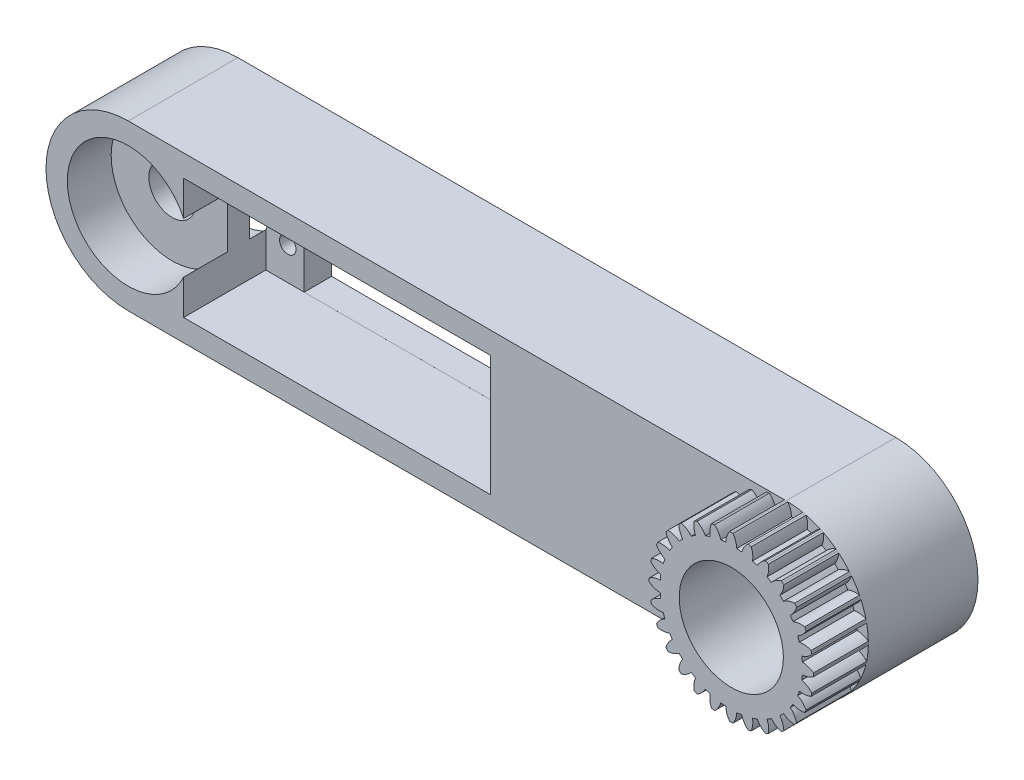
SolidWorks part; units mm, degrees
ref_plane "Front Plane" through (0, 0, 0) normal (0, 0, 1) x (1, 0, 0)
ref_plane "Top Plane" through (0, 0, 0) normal (0, 1, 0) x (1, 0, 0)
ref_plane "Right Plane" through (0, 0, 0) normal (1, 0, 0) x (0, 0, -1)
sketch "Sketch1" plane through (0, 0, 0) normal (0, 0, 1) x (1, 0, 0)
  line L0 (0, 0) -> (120, 0) construction
  line L1 (0, 15) -> (120, 15)
  line L2 (0, -15) -> (120, -15)
  circle A0 centre (0, 0) radius 15
  circle A1 centre (120, 0) radius 15
  dimension "D1" = 30
  dimension "D2" = 120
extrude "Boss-Extrude1" add sketch "Sketch1" along normal mid plane 20 contours A0 | A0 L0 A1 L1 | L0 A0 L2 A1 | A1 region at (60, 7.777, 0) region at (10.3066, -10.3066, 0) region at (60, -7.777, 0) region at (109.6934, 10.3066, 0)
sketch "Sketch3" plane through (0, 0, 10) normal (0, 0, 1) x (1, 0, 0)
  line L0 (0, 0) -> (94, 0) construction
  line L1 (90, 4.5) -> (120, 7.5)
  line L2 (90, -4.5) -> (120, -7.5)
  circle A0 centre (120, 0) radius 7.5
  circle A1 centre (90, 0) radius 4.5
  circle A2 centre (95.5, 0) radius 1.5
  circle A3 centre (120, 0) radius 4.25
  dimension "D2" = 15
  dimension "D3" = 9
  dimension "D5" = 3
  dimension "D7" = 8.5
  dimension "D1" = 120
  dimension "D4" = 30
  dimension "D6" = 24.5
extrude "Cut-Extrude5" cut sketch "Sketch3<3>" against normal blind 12 contours L1 A0 L2 A3 region at (119.2785, 7.2147, 10)
sketch "Sketch3<3>" plane through (0, 0, 10) normal (0, 0, 1) x (1, 0, 0) same geometry as "Sketch3"
extrude "Cut-Extrude6" cut sketch "Sketch3" against normal through all contours A3 region at (120, 0, 10)
sketch "Sketch4" plane through (0, 0, 10) normal (0, 0, 1) x (1, 0, 0)
  line L0 (0, 0) -> (120, 0) construction
  line L2 (59.1, -11) -> (17.1, -11)
  line L3 (59.1, -11) -> (59.1, 11)
  line L4 (59.1, 11) -> (17.1, 11)
  line L5 (17.1, -11) -> (17.1, 11)
  line L6 (59.1, -11) -> (17.1, 11) construction
  line L7 (59.1, 11) -> (17.1, -11) construction
  circle A0 centre (0, 0) radius 4.25
  circle A1 centre (0, 0) radius 11.11
  circle A2 centre (27.1, 0) radius 2.6569
  point P4 (38.1, 0)
  dimension "D3" = 8.5
  dimension "D4" = 22.22
  dimension "D1" = 22
  dimension "D2" = 42
  dimension "D5" = 27.1
  dimension "D6" = 10
extrude "Cut-Extrude8" cut sketch "Sketch4" against normal through all contours A0 | L3 L2 L5 L4
sketch "Sketch5" plane through (0, 0, -10) normal (0, 0, -1) x (-1, 0, 0)
  circle A0 centre (0, 0) radius 11.11
  dimension "D1" = 22.22
extrude "Cut-Extrude10" cut sketch "Sketch5" against normal blind 8
mirror "Mirror2" about plane through (0, 0, 0) normal (0, 0, 1) of "Cut-Extrude10"
sketch "Sketch7" plane through (0, 0, 10) normal (0, 0, 1) x (1, 0, 0)
  line L0 (38.1, 11) -> (38.1, -11) construction
  line L1 (59.1, 11) -> (17.1, 11) construction
  line L2 (59.1, -11) -> (17.1, -11) construction
  line L4 (66.1, -11.0014) -> (10.1, -11.0014)
  line L5 (66.1, -11.0014) -> (66.1, 11.0014)
  line L6 (66.1, 11.0014) -> (10.1, 11.0014)
  line L7 (10.1, -11.0014) -> (10.1, 11.0014)
  line L8 (66.1, -11.0014) -> (10.1, 11.0014) construction
  line L9 (66.1, 11.0014) -> (10.1, -11.0014) construction
  point P6 (38.1, 0)
  dimension "D2" = 56
extrude "Cut-Extrude12" cut sketch "Sketch7" against normal blind 15
sketch "Sketch8" plane through (0, 0, -5) normal (0, 0, 1) x (1, 0, 0)
  line L0 (38.1, 11.0014) -> (38.1, -11.0014) construction
  line L1 (66.1, 11.0014) -> (10.1, 11.0014) construction
  line L2 (10.1, -11.0014) -> (66.1, -11.0014) construction
  line L3 (14.1, 5) -> (14.1, -5) construction
  line L4 (62.1, 5) -> (62.1, -5) construction
  line L5 (38.1, 0) -> (25.4065, 0) construction
  line L6 (14.1, 0) -> (20.8073, 0) construction
  circle A0 centre (14.1, 5) radius 1.5
  circle A1 centre (14.1, -5) radius 1.5
  circle A2 centre (62.1, -5) radius 1.5
  circle A3 centre (62.1, 5) radius 1.5
  dimension "D1" = 3
  dimension "D2" = 10
  dimension "D3" = 48
extrude "Cut-Extrude13" cut sketch "Sketch8" against normal blind 14 contours A0 | A1 | A2 | A3 region at (14.1, 5, -5) region at (14.1, -5, -5) region at (62.1, -5, -5)
sketch "Sketch9" plane through (0, 0, 10) normal (0, 0, 1) x (1, 0, 0)
  circle A0 centre (120, 0) radius 9.5
  dimension "D1" = 19
extrude "Cut-Extrude14" cut sketch "Sketch9" against normal up to surface (12 mm away) up to face at (124.25, 0, -2)
sketch "Sketch10" plane through (0, 0, -10) normal (0, 0, -1) x (-1, 0, 0)
  circle A0 centre (-62.1, 5) radius 3.5
  circle A1 centre (-62.1, -5) radius 3.5
  circle A2 centre (-14.1, 5) radius 3.5
  circle A3 centre (-14.1, -5) radius 3.5
  dimension "D1" = 7
sketch "Sketch12" plane through (0, 0, 10) normal (0, 0, 1) x (1, 0, 0)
  line L0 (120, 0) -> (120, 29.5163) construction
  line L1 (120.3, 15) -> (119.7, 15)
  circle A0 centre (120, 0) radius 13
  circle A1 centre (120, 0) radius 2.65
  circle A2 centre (120, 0) radius 15 construction
  arc A3 (119.7, 15) -> (119, 12.9615) centre (122.738, 12.8174) ccw
  arc A4 (120.3, 15) -> (121, 12.9615) centre (117.262, 12.8174) cw
  arc A5 (119, 12.9615) -> (121, 12.9615) centre (120, 0) cw
  point P11 (120, 15)
  circle M3 centre (120, 0) radius 9.5
  arc M11 (120, -15) -> (120, 15) centre (120, 0) ccw
  line M12 (120, 15) -> (0, 15)
  dimension "D1" = 26
  dimension "D2" = 5.3
  dimension "D5" = 3.7407
  dimension "D6" = 2
  dimension "D3" = 1
  dimension "D4" = 0.6
sketch "Sketch14" plane through (0, 0, -2) normal (0, 0, 1) x (1, 0, 0)
  circle A0 centre (120, 0) radius 4.25
  circle A1 centre (120, 0) radius 9.5
sketch "Sketch15" plane through (0, 15, 0) normal (0, 1, 0) x (1, 0, 0)
  line L0 (109.75, -5.3165) -> (109.75, 4.6835)
  line L1 (109.75, 4.6835) -> (145.4367, 4.6835)
  line L2 (145.4367, 4.6835) -> (145.4367, -5.3165)
  line L3 (145.4367, -5.3165) -> (109.75, -5.3165)
  point P3 (109.75, -0.3165)
  dimension "D1" = 10
  dimension "D2" = 6
extrude "Boss-Extrude2" add sketch "Sketch12" along normal blind 10 contours A0 M3 region at (129.2696, 8.582, 10)
extrude "Boss-Extrude3" add sketch "Sketch12<5>" along normal blind 10 contours A4 A3 A0 M11 M12 region at (120, 13.842, 10)
sketch "Sketch12<5>" plane through (0, 0, 10) normal (0, 0, 1) x (1, 0, 0) same geometry as "Sketch12"
pattern_circular "CirPattern1" count 28 over 360 about axis through (120, 0, 20) along (0, 0, -1) of "Boss-Extrude3"
